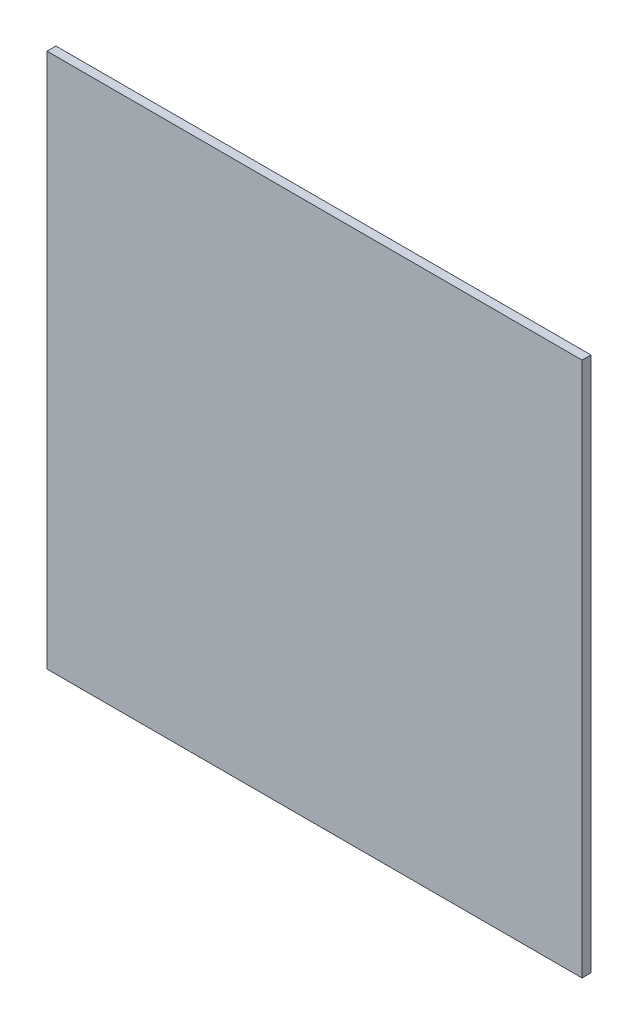
SolidWorks part; units mm, degrees
ref_plane "Ebene vorne" through (0, 0, 0) normal (0, 0, 1) x (1, 0, 0)
ref_plane "Ebene oben" through (0, 0, 0) normal (0, 1, 0) x (1, 0, 0)
ref_plane "Ebene rechts" through (0, 0, 0) normal (1, 0, 0) x (0, 0, -1)
sketch "Skizze1" plane through (0, 0, 0) normal (0, 0, 1) x (1, 0, 0)
  line L1 (300, -300) -> (-300, -300)
  line L2 (300, -300) -> (300, 300)
  line L3 (300, 300) -> (-300, 300)
  line L4 (-300, -300) -> (-300, 300)
  line L5 (300, -300) -> (-300, 300) construction
  line L6 (300, 300) -> (-300, -300) construction
  point P0 (0, 0)
  dimension "D1" = 600
  dimension "D2" = 600
extrude "Aufsatz-Linear austragen1" add sketch "Skizze1" along normal blind 10
